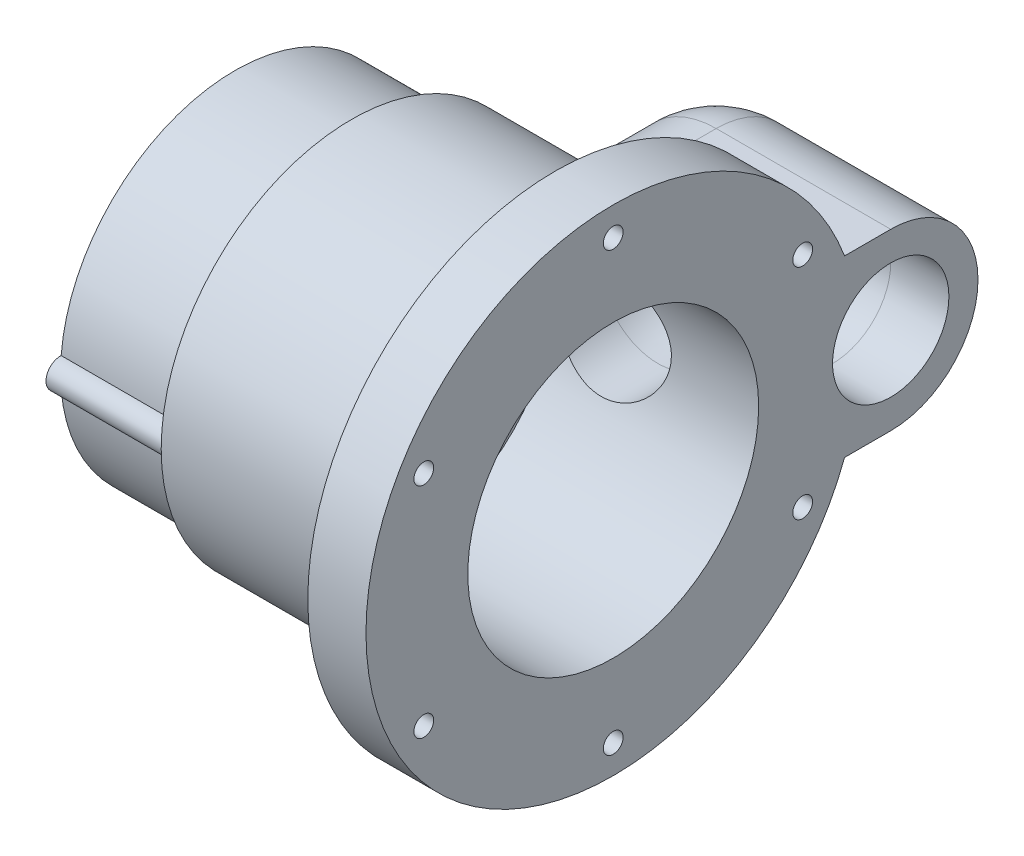
SolidWorks part; units mm, degrees
material "ABS"
ref_plane "Front" through (0, 0, 0) normal (0, 0, 1) x (1, 0, 0)
ref_plane "Top" through (0, 0, 0) normal (0, 1, 0) x (1, 0, 0)
ref_plane "Right" through (0, 0, 0) normal (1, 0, 0) x (0, 0, -1)
sketch "Croquis1" plane through (0, 0, 0) normal (1, 0, 0) x (0, 0, -1)
  arc A0 (-29.8958, -2.4978) -> (-29.8958, 2.4978) centre (0, 0) ccw
  arc A1 (-29.8958, 2.4978) -> (-29.8958, -2.4978) centre (-30, 0) ccw
  circle A2 centre (0, 0) radius 15
  dimension "D1" = 60
  dimension "D2" = 5
  dimension "D3" = 30
extrude "Saliente-Extruir1" add sketch "Croquis1" along normal mid plane 20
sketch "Croquis2" plane through (10, 0, 0) normal (1, 0, 0) x (0, 0, -1)
  circle A0 centre (0, 0) radius 32.7
  circle A1 centre (0, 0) radius 15
  dimension "D1" = 65.4
  dimension "D2" = 30
extrude "Saliente-Extruir2" add sketch "Croquis2" along normal blind 10
sketch "Croquis3" plane through (20, 0, 0) normal (1, 0, 0) x (0, 0, -1)
  circle A0 centre (0, 0) radius 32.7 construction
  circle A1 centre (0, 0) radius 32.7
  circle A2 centre (0, 0) radius 25
  dimension "D1" = 50
extrude "Saliente-Extruir3" add sketch "Croquis3" along normal blind 35
sketch "Croquis8" plane through (55, 0, 0) normal (1, 0, 0) x (0, 0, -1)
  line L3 (47.7, 0) -> (32.7, 0) construction
  line L4 (47.7, 15) -> (29.0567, 15)
  line L5 (47.7, -15) -> (29.0567, -15)
  arc A3 (47.7, -15) -> (47.7, 15) centre (47.7, 0) ccw
  circle A4 centre (0, 0) radius 32.7 construction
  arc A5 (29.0567, -15) -> (29.0567, 15) centre (0, 0) ccw
  dimension "D1" = 30
  dimension "D2" = 15
extrude "Saliente-Extruir4" add sketch "Croquis8" against normal up to surface (45 mm away) up to face at (10, 0, 1.25)
sketch "Croquis22" plane through (55, 0, 0) normal (1, 0, 0) x (0, 0, -1)
  line L0 (29.0567, -15) -> (47.7, -15) construction
  line L1 (47.7, 15) -> (29.0567, 15) construction
  line L2 (29.0567, -15) -> (39.7649, -15)
  line L3 (39.7649, 15) -> (29.0567, 15)
  circle A0 centre (0, 0) radius 42.5
  arc A1 (29.0567, 15) -> (29.0567, -15) centre (0, 0) ccw construction
  arc A2 (29.0567, 15) -> (29.0567, -15) centre (0, 0) ccw
  arc M2 (29.0567, 15) -> (29.0567, -15) centre (0, 0) ccw
  line M3 (29.0567, -15) -> (47.7, -15)
  line M5 (47.7, 15) -> (29.0567, 15)
  dimension "D1" = 85
extrude "Saliente-Extruir5" add sketch "Croquis22" against normal blind 10 contours A0 M5 M3 M2 region at (55, -16.1829, -34.4108)
hole_wizard "Taladro de margen para M31" positions "Croquis24" profile "Croquis25" hole size "M3" standard "Ansi Metric" end condition up to next
sketch "Croquis24" plane through (45, 0, 0) normal (-1, 0, 0) x (0, 0, 1)
  line L0 (0, -35.75) -> (0, 35.75) construction
  line L1 (0, 42.5) -> (0, 32.7) construction
  arc A0 (-39.7649, -15) -> (-39.7649, 15) centre (0, 0) ccw construction
  arc A1 (-29.0567, -15) -> (-29.0567, 15) centre (0, 0) ccw construction
  point P0 (0, 37.6)
  point P17 (0, 37.6)
  point P23 (32.5626, 18.8)
  point P24 (32.5626, -18.8)
  point P25 (0, -37.6)
  point P26 (-32.5626, -18.8)
  point P27 (-32.5626, 18.8)
  dimension "D1" = 6
sketch "Croquis25" plane through (45, 37.6, 0) normal (0, 1, 0) x (0, 0, 1)
  line L0 (0, 0) -> (0, 10)
  line L1 (0, 10) -> (1.7, 10)
  line L2 (1.7, 10) -> (1.7, 0)
  line L5 (1.7, 0) -> (0, 0)
  line L11 (0, -6.35) -> (0, 107.95) construction
  dimension "Diámetro de taladro hasta el siguiente" = 3.4
  dimension "Profundidad de taladro hasta el siguiente" = 10
fillet "Redondeo1" radius 15 3 edges at (10, 15, -38.3783) (10, -15, -38.3783) (10, 0, -62.7)
sketch "Croquis17" plane through (0, 0, 0) normal (0, 1, 0) x (1, 0, 0)
  line L0 (55, 47.7) -> (45, 47.7)
  line L1 (25, 47.7) -> (55, 47.7) construction
  line L2 (30, 32.7) -> (30, 0)
  line L3 (-35.75, 0) -> (35.75, 0) construction
  line L4 (10, 32.7) -> (10, 47.7) construction
  arc A0 (45, 47.7) -> (30, 32.7) centre (45, 32.7) ccw
  point P12 (30, 47.7)
  dimension "D2" = 15
  dimension "D1" = 20
sweep "Cortar-Barrer4" cut path "Croquis17" circular profile diameter 20 parameters "D3"=20
fillet "Redondeo2" radius 10 1 edges at (20, 0, -15)
sketch "Croquis27" plane through (45, 0, 0) normal (-1, 0, 0) x (0, 0, 1)
  line L0 (0, -35.75) -> (0, 35.75) construction
  line L1 (0, 40.78) -> (-2.754, 39.19)
  line L2 (-2.754, 39.19) -> (-2.754, 36.01)
  line L3 (-2.754, 36.01) -> (0, 34.42)
  line L4 (0, 34.42) -> (2.754, 36.01)
  line L5 (2.754, 36.01) -> (2.754, 39.19)
  line L6 (2.754, 39.19) -> (0, 40.78)
  line L7 (35.3165, 20.39) -> (32.5626, 21.98)
  line L8 (32.5626, 21.98) -> (29.8086, 20.39)
  line L9 (29.8086, 20.39) -> (29.8086, 17.21)
  line L10 (29.8086, 17.21) -> (32.5626, 15.62)
  line L11 (32.5626, 15.62) -> (35.3165, 17.21)
  line L12 (35.3165, 17.21) -> (35.3165, 20.39)
  line L13 (35.3165, -20.39) -> (35.3165, -17.21)
  line L14 (35.3165, -17.21) -> (32.5626, -15.62)
  line L15 (32.5626, -15.62) -> (29.8086, -17.21)
  line L16 (29.8086, -17.21) -> (29.8086, -20.39)
  line L17 (29.8086, -20.39) -> (32.5626, -21.98)
  line L18 (32.5626, -21.98) -> (35.3165, -20.39)
  line L19 (0, -40.78) -> (2.754, -39.19)
  line L20 (2.754, -39.19) -> (2.754, -36.01)
  line L21 (2.754, -36.01) -> (0, -34.42)
  line L22 (0, -34.42) -> (-2.754, -36.01)
  line L23 (-2.754, -36.01) -> (-2.754, -39.19)
  line L24 (-2.754, -39.19) -> (0, -40.78)
  line L25 (-35.3165, -20.39) -> (-32.5626, -21.98)
  line L26 (-32.5626, -21.98) -> (-29.8086, -20.39)
  line L27 (-29.8086, -20.39) -> (-29.8086, -17.21)
  line L28 (-29.8086, -17.21) -> (-32.5626, -15.62)
  line L29 (-32.5626, -15.62) -> (-35.3165, -17.21)
  line L30 (-35.3165, -17.21) -> (-35.3165, -20.39)
  line L31 (-35.3165, 20.39) -> (-35.3165, 17.21)
  line L32 (-35.3165, 17.21) -> (-32.5626, 15.62)
  line L33 (-32.5626, 15.62) -> (-29.8086, 17.21)
  line L34 (-29.8086, 17.21) -> (-29.8086, 20.39)
  line L35 (-29.8086, 20.39) -> (-32.5626, 21.98)
  line L36 (-32.5626, 21.98) -> (-35.3165, 20.39)
  circle A0 centre (0, 37.6) radius 2.754 construction
  circle A1 centre (32.5626, 18.8) radius 2.754 construction
  circle A2 centre (32.5626, -18.8) radius 2.754 construction
  circle A3 centre (0, -37.6) radius 2.754 construction
  circle A4 centre (-32.5626, -18.8) radius 2.754 construction
  circle A5 centre (-32.5626, 18.8) radius 2.754 construction
  dimension "D1" = 3.18
  dimension "D2" = 6
extrude "Cortar-Extruir1" cut sketch "Croquis27" against normal blind 5
